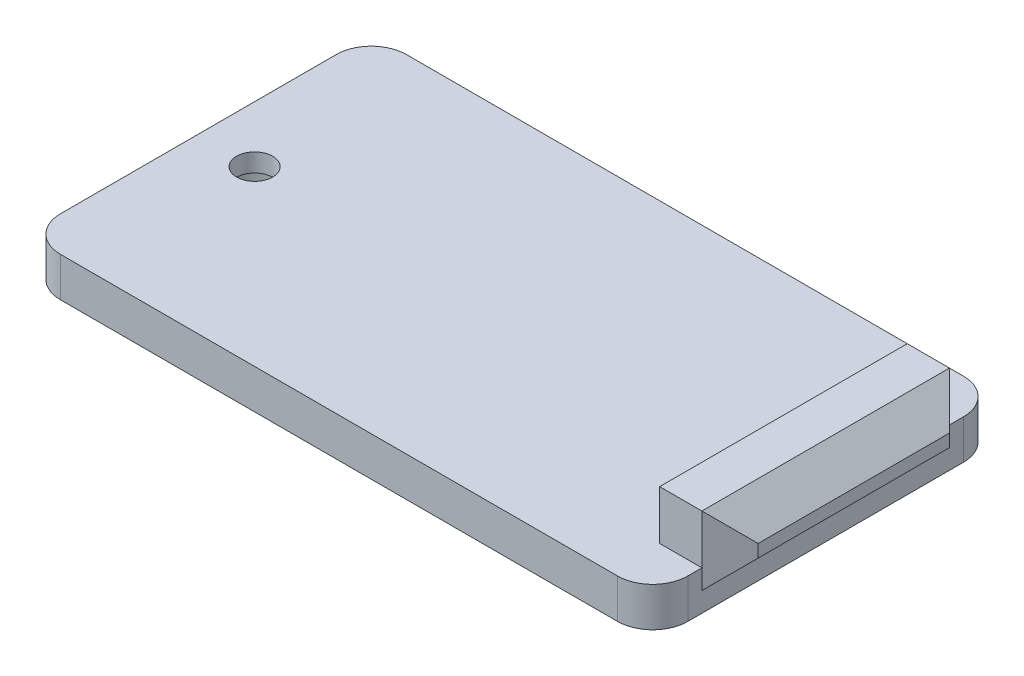
SolidWorks part; units mm, degrees
ref_plane "Front Plane" through (0, 0, 0) normal (0, 0, 1) x (1, 0, 0)
ref_plane "Top Plane" through (0, 0, 0) normal (0, 1, 0) x (1, 0, 0)
ref_plane "Right Plane" through (0, 0, 0) normal (1, 0, 0) x (0, 0, -1)
sketch "Sketch1" plane through (0, 0, 0) normal (0, 1, 0) x (1, 0, 0)
  line L0 (0, 15.621) -> (56.642, 15.621) construction
  line L1 (3.175, 0) -> (53.467, 0)
  line L2 (0, 3.175) -> (0, 28.067)
  line L3 (3.175, 31.242) -> (53.467, 31.242)
  line L4 (56.642, 3.175) -> (56.642, 28.067)
  arc A0 (3.175, 31.242) -> (0, 28.067) centre (3.175, 28.067) ccw
  arc A1 (56.642, 28.067) -> (53.467, 31.242) centre (53.467, 28.067) ccw
  arc A2 (53.467, 0) -> (56.642, 3.175) centre (53.467, 3.175) ccw
  arc A3 (0, 3.175) -> (3.175, 0) centre (3.175, 3.175) ccw
  circle A4 centre (5.08, 15.621) radius 1.632
  dimension "D3" = 6.35
  dimension "D1" = 3.2639
  dimension "D2" = 5.08
  dimension "D4" = 3.175
  dimension "D5" = 3.175
  dimension "D6" = 50.292
  dimension "D7" = 24.892
extrude "Boss-Extrude1" add sketch "Sketch1" along normal blind 3.556
sketch "Sketch2" plane through (0, 0, 0) normal (0, -1, 0) x (1, 0, 0)
  circle A0 centre (5.08, -15.621) radius 3.175
  circle A1 centre (5.08, -15.621) radius 1.6319
  dimension "D1" = 6.35
extrude "Cut-Extrude1" cut sketch "Sketch2" against normal blind 1.905
sketch "Sketch3" plane through (56.642, 0, 0) normal (1, 0, 0) x (0, 0, -1)
  line L0 (3.175, 3.556) -> (3.175, 0) construction
  line L1 (4.445, 1.5875) -> (26.797, 1.5875)
  line L2 (4.445, 1.5875) -> (4.445, 8.1915)
  line L3 (4.445, 8.1915) -> (26.797, 8.1915)
  line L4 (26.797, 1.5875) -> (26.797, 8.1915)
  line L5 (28.067, 3.556) -> (28.067, 0) construction
  line L6 (3.175, 0) -> (28.067, 0) construction
  dimension "D1" = 1.27
  dimension "D2" = 1.27
  dimension "D3" = 1.5875
  dimension "D4" = 6.604
extrude "Boss-Extrude2" add sketch "Sketch3" along normal blind 2.54
chamfer "Chamfer1" distance 2.7305 angle 45 2 edges at (59.182, 1.5875, -15.621) (59.182, 8.1915, -15.621)
sketch "Sketch4" plane through (56.642, 0, 0) normal (-1, 0, 0) x (0, 0, 1)
  line L5 (-26.797, 8.001) -> (-4.445, 8.001)
  line L6 (-26.797, 8.001) -> (-26.797, 3.556)
  line L7 (-26.797, 3.556) -> (-4.445, 3.556)
  line L8 (-4.445, 8.001) -> (-4.445, 3.556)
extrude "Boss-Extrude3" add sketch "Sketch4" along normal blind 3.81
sketch "Sketch5" plane through (0, 0, 0) normal (0, -1, 0) x (1, 0, 0)
  line L0 (12.7, -9.9279) -> (12.7, -31.242) construction
  line L2 (53.467, -31.242) -> (3.175, -31.242) construction
  line L3 (0, -28.067) -> (0, -3.175) construction
  line L4 (0, -15.621) -> (56.642, -15.621) construction
  line L5 (56.642, -26.797) -> (56.642, -4.445) construction
  line L6 (11.1125, -9.271) -> (11.1141, -21.9)
  line L7 (14.2875, -9.271) -> (14.2859, -21.9)
  arc A0 (14.2875, -9.271) -> (11.1125, -9.271) centre (12.7, -9.271) ccw
  arc A1 (11.1141, -21.9) -> (14.2859, -21.9) centre (12.7, -21.971) ccw
  dimension "D2" = 3.175
  dimension "D3" = 3.175
  dimension "D1" = 12.7
  dimension "D4" = 12.7
  dimension "D5" = 6.35
extrude "Cut-Extrude2" cut sketch "Sketch5" against normal blind 1.778
sketch "Sketch6" plane through (0, 0, 0) normal (0, -1, 0) x (1, 0, 0)
  line L0 (14.2871, -12.5095) -> (56.642, -12.5095) construction
  line L1 (14.2859, -21.9) -> (14.2875, -9.271) construction
  line L2 (56.642, -26.797) -> (56.642, -4.445) construction
  line L3 (53.467, -31.242) -> (3.175, -31.242) construction
  text T0 "<b>PGM PIN</b>" font "Arial Rounded MT Bold" height 6.35
  dimension "D1" = 18.7325
extrude "Cut-Extrude3" cut sketch "Sketch6" against normal blind 0.4
chamfer "Chamfer2" distance 2.54 angle 45 2 edges at (59.182, 4.8895, -4.445) (59.182, 4.8895, -26.797)
sketch "Sketch7" plane through (0, 0.4, 0) normal (0, -1, 0) x (1, 0, 0)
  line L0 (22.8836, -17.8227) -> (22.8836, -13.204) construction
  line L1 (21.5342, -13.204) -> (21.5342, -16.637) construction
  line L2 (21.5342, -16.637) -> (19.4705, -13.1805) construction
  line L3 (17.6449, -13.2983) -> (17.6449, -18.0062) construction
  line L4 (18.9942, -18.0013) -> (18.9942, -14.4939) construction
  line L5 (18.9942, -14.4939) -> (21.1101, -17.9827) construction
  line L6 (24.233, -13.2487) -> (24.233, -17.9653) construction
  line L7 (25.6617, -17.9653) -> (25.6617, -13.2487) construction
  line L8 (29.411, -17.5895) -> (30.1067, -17.5895) construction
  line L9 (30.1067, -17.5895) -> (30.1067, -15.9226) construction
  line L10 (30.1067, -15.9226) -> (29.411, -15.9226) construction
  line L11 (29.0811, -18.7007) -> (30.671, -18.7007) construction
  line L12 (31.5355, -17.8748) -> (31.5355, -13.2437) construction
  line L13 (30.1067, -13.2326) -> (30.1067, -14.8114) construction
  line L14 (30.1067, -14.8114) -> (29.1034, -14.8114) construction
  line L15 (37.0322, -13.4992) -> (36.298, -17.272) construction
  line L16 (36.298, -17.272) -> (36.298, -13.1991) construction
  line L17 (34.9486, -13.1978) -> (34.9486, -17.9529) construction
  line L18 (35.8651, -18.7007) -> (36.2422, -18.7007) construction
  line L19 (37.2083, -17.8313) -> (37.9673, -14.5732) construction
  line L20 (37.9673, -14.5732) -> (38.7301, -17.8313) construction
  line L21 (39.7694, -18.7007) -> (40.1452, -18.7007) construction
  line L22 (40.9811, -17.9529) -> (40.9811, -13.1978) construction
  line L23 (39.6317, -13.1991) -> (39.6317, -17.272) construction
  line L24 (39.6317, -17.272) -> (38.9025, -13.5984) construction
  line L25 (43.0895, -15.8432) -> (44.4947, -15.8432) construction
  line L26 (44.3347, -14.732) -> (43.4417, -14.732) construction
  line L27 (43.4417, -14.732) -> (43.4417, -13.9209) construction
  line L28 (42.0924, -13.8924) -> (42.0924, -15.021) construction
  line L29 (51.2267, -18.7007) -> (52.8167, -18.7007) construction
  line L30 (53.6811, -17.8748) -> (53.6811, -13.2437) construction
  line L31 (52.2524, -13.2326) -> (52.2524, -14.8114) construction
  line L32 (52.2524, -14.8114) -> (51.249, -14.8114) construction
  line L33 (22.8836, -17.8227) -> (22.8836, -13.204)
  line L34 (21.5342, -13.204) -> (21.5342, -16.637)
  line L35 (21.5342, -16.637) -> (19.4705, -13.1805)
  line L36 (17.6449, -13.2983) -> (17.6449, -18.0062)
  line L37 (18.9942, -18.0013) -> (18.9942, -14.4939)
  line L38 (18.9942, -14.4939) -> (21.1101, -17.9827)
  line L39 (24.233, -13.2487) -> (24.233, -17.9653)
  line L40 (25.6617, -17.9653) -> (25.6617, -13.2487)
  line L41 (29.411, -17.5895) -> (30.1067, -17.5895)
  line L42 (30.1067, -17.5895) -> (30.1067, -15.9226)
  line L43 (30.1067, -15.9226) -> (29.411, -15.9226)
  line L44 (29.0811, -18.7007) -> (30.671, -18.7007)
  line L45 (31.5355, -17.8748) -> (31.5355, -13.2437)
  line L46 (30.1067, -13.2326) -> (30.1067, -14.8114)
  line L47 (30.1067, -14.8114) -> (29.1034, -14.8114)
  line L48 (37.0322, -13.4992) -> (36.298, -17.272)
  line L49 (36.298, -17.272) -> (36.298, -13.1991)
  line L50 (34.9486, -13.1978) -> (34.9486, -17.9529)
  line L51 (35.8651, -18.7007) -> (36.2422, -18.7007)
  line L52 (37.2083, -17.8313) -> (37.9673, -14.5732)
  line L53 (37.9673, -14.5732) -> (38.7301, -17.8313)
  line L54 (39.7694, -18.7007) -> (40.1452, -18.7007)
  line L55 (40.9811, -17.9529) -> (40.9811, -13.1978)
  line L56 (39.6317, -13.1991) -> (39.6317, -17.272)
  line L57 (39.6317, -17.272) -> (38.9025, -13.5984)
  line L58 (43.0895, -15.8432) -> (44.4947, -15.8432)
  line L59 (44.3347, -14.732) -> (43.4417, -14.732)
  line L60 (43.4417, -14.732) -> (43.4417, -13.9209)
  line L61 (42.0924, -13.8924) -> (42.0924, -15.021)
  line L62 (51.2267, -18.7007) -> (52.8167, -18.7007)
  line L63 (53.6811, -17.8748) -> (53.6811, -13.2437)
  line L64 (52.2524, -13.2326) -> (52.2524, -14.8114)
  line L65 (52.2524, -14.8114) -> (51.249, -14.8114)
  line L69 (51.5566, -17.5895) -> (52.2524, -17.5895)
  line L70 (52.2524, -17.5895) -> (52.2524, -15.9226)
  line L71 (52.2524, -15.9226) -> (51.5566, -15.9226)
  line L72 (51.5566, -17.5895) -> (52.2524, -17.5895)
  line L73 (52.2524, -17.5895) -> (52.2524, -15.9226)
  line L74 (52.2524, -15.9226) -> (51.5566, -15.9226)
  spline S0 degree 3 poles (1694.5755, 1077.0446) (-0.9521, -10.018) (16.4237, -10.1614) (21.3024, -18.2955) (21.3908, -18.4248) (21.4855, -18.5395) (21.6023, -18.636) (21.7165, -18.702) (21.8212, -18.7424) (21.909, -18.7651) (25.6619, -19.2283) (30.4113, -0.5881) (-74.1786, -2016.3877) knots -20.662899 -20.662899 -20.662899 -20.662899 0.149245 0.276601 0.389391 0.49681 0.605632 0.72403 0.787951 0.85429 0.924647 9.163349 9.163349 9.163349 9.163349 only from (21.1101, -17.9827) to (22.1035, -18.7801) construction
  spline S1 degree 3 poles (219.4888, -2008.9999) (13.2158, 3.8808) (19.0049, -19.4639) (22.3265, -18.7508) (22.432, -18.7088) (22.5312, -18.6519) (22.6234, -18.5835) (22.7009, -18.502) (24.5279, -16.1058) (3.0005, -0.21) (1757.2202, -1014.0759) knots -10.891564 -10.891564 -10.891564 -10.891564 0.125807 0.249903 0.374306 0.502706 0.630625 0.755401 0.87671 10.617247 10.617247 10.617247 10.617247 only from (22.1035, -18.7801) to (22.8142, -18.3126) construction
  spline S2 degree 3 poles (1955.4913, -532.5395) (-0.8488, -18.4154) (22.3614, -21.2427) (22.868, -18.0952) (23.3749, -13.5564) (0.9699, -7.6141) (2019.659, -130.1936) knots -18.460388 -18.460388 -18.460388 -18.460388 0.206623 0.439918 0.70566 27.741178 27.741178 27.741178 27.741178 only from (22.8142, -18.3126) to (22.8836, -17.8227) construction
  spline S3 degree 3 poles (2015.117, 161.9076) (-4.3478, -24.2033) (23.7389, -17.199) (22.8457, -12.8793) (22.7913, -12.7442) (22.7151, -12.631) (22.6207, -12.5408) (22.5099, -12.4763) (19.3608, -11.4724) (11.7065, -41.2288) (305.4229, 1967.3468) knots -11.230317 -11.230317 -11.230317 -11.230317 0.155135 0.293175 0.420208 0.539589 0.652988 0.763719 0.877627 9.330939 9.330939 9.330939 9.330939 only from (22.8836, -13.204) to (22.2486, -12.4301) construction
  spline S4 degree 3 poles (-221.9847, 1972.5129) (33.2019, -41.098) (25.6271, -11.4529) (21.9492, -12.4775) (21.8233, -12.5449) (21.7187, -12.639) (21.6359, -12.7554) (21.576, -12.8898) (20.6395, -16.9841) (48.7131, -24.0672) (-1968.7834, 183.0792) knots -9.165477 -9.165477 -9.165477 -9.165477 0.133965 0.257434 0.373611 0.491036 0.609102 0.73139 0.859882 11.130855 11.130855 11.130855 11.130855 only from (22.2486, -12.4301) to (21.5342, -13.204) construction
  spline S5 degree 3 poles (1656.6632, 1135.4192) (16.0773, -34.8465) (23.9453, -19.395) (19.2712, -12.8948) (19.168, -12.7596) (19.0501, -12.6437) (18.9231, -12.5453) (18.7807, -12.4775) (14.9393, -11.4463) (7.1492, -42.1909) (257.016, 1973.2581) knots -17.714942 -17.714942 -17.714942 -17.714942 0.132477 0.263732 0.391458 0.516373 0.636572 0.752789 0.870676 9.55723 9.55723 9.55723 9.55723 only from (19.4705, -13.1805) to (18.4572, -12.4301) construction
  spline S6 degree 3 poles (-199.2692, 1975.6658) (30.3091, -42.3393) (22.3802, -11.4241) (18.1045, -12.478) (17.9603, -12.5449) (17.8435, -12.6436) (17.7512, -12.769) (17.6894, -12.923) (16.68, -17.5496) (47.2481, -25.402) (-1972.9092, 179.8342) knots -9.252194 -9.252194 -9.252194 -9.252194 0.140574 0.265343 0.378552 0.487786 0.598508 0.718065 0.850401 10.972845 10.972845 10.972845 10.972845 only from (18.4572, -12.4301) to (17.6449, -13.2983) construction
  spline S7 degree 3 poles (-1971.9914, -221.0692) (45.7061, -7.1326) (16.7501, -14.3175) (17.6857, -18.322) (17.7427, -18.457) (17.8227, -18.5739) (17.9276, -18.6675) (18.0551, -18.7345) (21.9641, -19.7378) (29.2769, 9.5928) (-196.239, -2007.1892) knots -9.821137 -9.821137 -9.821137 -9.821137 0.139787 0.268103 0.388435 0.504223 0.619109 0.736039 0.86109 10.613704 10.613704 10.613704 10.613704 only from (17.6449, -18.0062) to (18.3654, -18.7801) construction
  spline S8 degree 3 poles (285.63, -2000.738) (8.0695, 9.4364) (15.4308, -19.7154) (18.6248, -18.7353) (18.7345, -18.6708) (18.8287, -18.5817) (18.9032, -18.4678) (18.9582, -18.332) (19.8193, -13.7643) (-7.3619, -7.0829) (2014.0061, -158.3941) knots -8.414127 -8.414127 -8.414127 -8.414127 0.121086 0.23344 0.343994 0.455662 0.57424 0.702085 0.841831 12.827612 12.827612 12.827612 12.827612 only from (18.3654, -18.7801) to (18.9942, -18.0013) construction
  spline S9 degree 3 poles (2015.8485, 184.4309) (-3.4376, -24.7913) (26.5834, -17.2335) (25.6202, -12.9015) (25.5631, -12.7572) (25.4784, -12.6394) (25.3767, -12.5468) (25.262, -12.4769) (21.9114, -11.4795) (14.7129, -40.1038) (275.6513, 1971.7398) knots -10.696765 -10.696765 -10.696765 -10.696765 0.157586 0.29838 0.425876 0.546132 0.660428 0.770664 0.881724 9.364177 9.364177 9.364177 9.364177 only from (25.6617, -13.2487) to (24.9932, -12.4301) construction
  spline S10 degree 3 poles (-202.4906, 1974.5266) (36.1726, -41.848) (28.5549, -11.4334) (24.6724, -12.4784) (24.5387, -12.5492) (24.4273, -12.6474) (24.3387, -12.7689) (24.2771, -12.9117) (23.2907, -17.1097) (52.9605, -24.6484) (-1964.8958, 194.4319) knots -9.066225 -9.066225 -9.066225 -9.066225 0.135671 0.258584 0.375206 0.491184 0.60762 0.728719 0.85756 10.764543 10.764543 10.764543 10.764543 only from (24.9932, -12.4301) to (24.233, -13.2487) construction
  spline S11 degree 3 poles (-1966.1581, -213.3588) (52.5085, -6.7201) (23.3014, -14.0619) (24.2766, -18.3016) (24.3392, -18.444) (24.4269, -18.5653) (24.5389, -18.6624) (24.6727, -18.7316) (28.5344, -19.7815) (36.2765, 10.7612) (-210.5409, -2004.8083) knots -9.871041 -9.871041 -9.871041 -9.871041 0.141749 0.271807 0.392253 0.508926 0.624493 0.740892 0.864054 10.044378 10.044378 10.044378 10.044378 only from (24.233, -17.9653) to (24.9932, -18.7801) construction
  spline S12 degree 3 poles (296.3055, -2000.247) (14.3991, 9.2996) (21.9419, -19.7415) (25.2631, -18.7328) (25.3788, -18.6656) (25.4801, -18.5731) (25.5625, -18.4554) (25.6206, -18.3122) (26.5783, -13.9553) (-3.3031, -6.554) (2016.8183, -204.938) knots -8.324459 -8.324459 -8.324459 -8.324459 0.119507 0.230748 0.341537 0.454545 0.574394 0.701135 0.842157 11.766884 11.766884 11.766884 11.766884 only from (24.9932, -18.7801) to (25.6617, -17.9653) construction
  spline S13 degree 3 poles (-1141.57, -1639.3969) (37.7723, 4.8762) (26.0647, -16.1496) (28.5071, -17.457) (28.6151, -17.497) (28.7398, -17.5323) (28.8829, -17.5566) (29.0429, -17.5771) (36.1961, -17.9955) (43.6576, 0.9749) (13.0193, -2017.4401) knots -7.112256 -7.112256 -7.112256 -7.112256 0.082202 0.173662 0.275948 0.391262 0.521073 0.665415 0.824521 19.752253 19.752253 19.752253 19.752253 only from (28.3431, -17.3464) to (29.411, -17.5895) construction
  spline S14 degree 3 poles (-35.0501, 1982.9336) (42.7836, -38.1259) (35.4441, -15.3837) (29.0175, -15.9412) (28.8465, -15.9663) (28.6943, -16.003) (28.5598, -16.0511) (28.443, -16.1114) (28.3445, -16.1861) (28.2618, -16.2721) (28.1991, -16.3738) (28.154, -16.4893) (27.3637, -20.2232) (54.0403, -26.533) (-1963.7752, 161.9613) knots -10.706041 -10.706041 -10.706041 -10.706041 0.119625 0.228284 0.326363 0.415267 0.495857 0.570243 0.639451 0.706531 0.77329 0.842541 0.917764 7.268042 7.268042 7.268042 7.268042 only from (29.411, -15.9226) to (28.1224, -16.7598) construction
  spline S15 degree 3 poles (-1952.1927, -296.1847) (58.1274, -4.8115) (27.0921, -13.2814) (28.1735, -17.0867) (29.6461, -20.2637) (58.4433, -4.7638) (-1619.0052, -1151.4131) knots -17.588032 -17.588032 -17.588032 -17.588032 0.269063 0.519036 0.759812 16.445294 16.445294 16.445294 16.445294 only from (28.1224, -16.7598) to (28.3431, -17.3464) construction
  spline S16 degree 3 poles (-41.9846, 1983.8314) (45.3761, -40.1417) (36.3747, -14.0962) (28.5459, -14.8405) (28.2911, -14.8788) (28.0556, -14.9359) (27.8379, -15.0079) (27.6383, -15.0949) (27.4587, -15.2018) (27.2963, -15.3216) (27.1541, -15.4581) (27.0304, -15.6078) (26.9251, -15.7712) (26.8414, -15.949) (26.7731, -16.1388) (26.7269, -16.3429) (25.9325, -22.6554) (51.2956, -30.5501) (-1970.3258, 90.9039) knots -6.410635 -6.410635 -6.410635 -6.410635 0.081805 0.159007 0.231173 0.299492 0.363591 0.424766 0.483204 0.53989 0.595011 0.649378 0.703763 0.758786 0.81516 0.873993 0.935286 6.184234 6.184234 6.184234 6.184234 only from (29.1034, -14.8114) to (26.6936, -16.7858) construction
  spline S17 degree 3 poles (-1969.3893, -140.0701) (51.6371, -3.9375) (25.9499, -11.4626) (26.7257, -17.1977) (26.7665, -17.393) (26.8278, -17.5782) (26.9059, -17.7532) (27.0027, -17.9162) (27.1185, -18.066) (27.2493, -18.2044) (27.3998, -18.3268) (27.5676, -18.4322) (32.6459, -20.8359) (47.4639, 2.6822) (-664.7553, -1894.6989) knots -7.048453 -7.048453 -7.048453 -7.048453 0.088961 0.174891 0.258882 0.340892 0.421162 0.500878 0.579938 0.660187 0.741194 0.824606 0.910207 7.826152 7.826152 7.826152 7.826152 only from (26.6936, -16.7858) to (27.9524, -18.5854) construction
  spline S18 degree 3 poles (-461.0485, -1957.8289) (24.0357, 0.2052) (23.9754, -17.7978) (28.1727, -18.6377) (28.2977, -18.6574) (28.4334, -18.6734) (28.5798, -18.6857) (28.7375, -18.6937) (35.7709, -18.9905) (43.1078, -1.3668) (9.9605, -2018.5164) knots -10.968522 -10.968522 -10.968522 -10.968522 0.093582 0.195965 0.307413 0.42705 0.556114 0.694736 0.843057 19.111476 19.111476 19.111476 19.111476 only from (27.9524, -18.5854) to (29.0811, -18.7007) construction
  spline S19 degree 3 poles (123.9355, -2016.4485) (22.4379, 0.8817) (27.1719, -19.093) (30.8748, -18.6893) (30.9674, -18.6751) (31.0529, -18.6541) (31.1316, -18.6271) (31.2024, -18.5933) (31.2671, -18.5548) (31.3241, -18.5087) (31.375, -18.4556) (31.418, -18.3948) (31.4546, -18.3265) (31.4839, -18.2506) (31.5078, -18.1672) (31.5232, -18.0761) (31.9325, -14.114) (13.6058, -9.1312) (2028.9036, -118.2922) knots -7.859646 -7.859646 -7.859646 -7.859646 0.077201 0.149354 0.216632 0.280407 0.340294 0.396897 0.450458 0.503438 0.555489 0.60953 0.664538 0.723366 0.785866 0.85241 0.92367 9.425162 9.425162 9.425162 9.425162 only from (30.671, -18.7007) to (31.5355, -17.8748) construction
  spline S20 degree 3 poles (2024.5224, 153.4495) (3.4334, -24.4212) (32.4228, -17.3367) (31.4958, -12.8999) (31.4372, -12.7578) (31.3561, -12.6387) (31.2536, -12.5461) (31.1365, -12.4766) (27.6638, -11.4763) (20.4785, -40.3907) (269.8756, 1973.1764) knots -10.879349 -10.879349 -10.879349 -10.879349 0.15481 0.29374 0.419708 0.538233 0.652017 0.763548 0.877091 9.613357 9.613357 9.613357 9.613357 only from (31.5355, -13.2437) to (30.8583, -12.4301) construction
  spline S21 degree 3 poles (-192.9819, 1974.8971) (41.7689, -41.3433) (34.3515, -11.4431) (30.5459, -12.4783) (30.4149, -12.55) (30.3036, -12.6463) (30.2142, -12.7655) (30.1524, -12.9056) (29.1429, -16.8859) (59.2654, -24.6048) (-1956.5875, 216.7235) knots -9.063499 -9.063499 -9.063499 -9.063499 0.133395 0.256831 0.374018 0.491652 0.610199 0.730976 0.859706 10.470605 10.470605 10.470605 10.470605 only from (30.8583, -12.4301) to (30.1067, -13.2326) construction
  spline S22 degree 3 poles (2025.2351, 218.3807) (36.3034, -39.4717) (41.2772, -25.9219) (38.8533, -13.3404) (38.8269, -13.2298) (38.7947, -13.1009) (38.747, -12.9534) (38.6808, -12.8168) (38.6149, -12.7167) (38.5564, -12.6477) (38.487, -12.5867) (38.409, -12.5323) (38.3221, -12.485) (38.2241, -12.4538) (34.9329, -11.8089) (29.2405, -35.9793) (223.6773, 1978.7209) knots -23.288307 -23.288307 -23.288307 -23.288307 0.085751 0.163161 0.233313 0.294435 0.407254 0.517243 0.57198 0.626896 0.68281 0.74114 0.801241 0.863651 0.929305 6.936938 6.936938 6.936938 6.936938 only from (38.9025, -13.5984) to (38.0045, -12.4301) construction
  spline S23 degree 3 poles (-121.2426, 1981.1451) (48.7647, -39.2041) (42.0185, -11.5876) (37.6839, -12.4673) (37.5515, -12.5239) (37.4423, -12.6017) (37.354, -12.6908) (37.2797, -12.7814) (37.2216, -12.8745) (37.1809, -12.9737) (37.1497, -13.0824) (37.1134, -13.2047) (34.4734, -22.5334) (43.2594, -34.9159) (-1900.4937, 482.1352) knots -7.932757 -7.932757 -7.932757 -7.932757 0.107759 0.20426 0.291925 0.375204 0.453432 0.526045 0.594111 0.657905 0.725931 0.805738 0.896595 18.867428 18.867428 18.867428 18.867428 only from (38.0045, -12.4301) to (37.0322, -13.4992) construction
  spline S24 degree 3 poles (2030.5792, 136.7004) (9.4802, -24.0699) (37.1401, -17.3276) (36.261, -12.8702) (36.2046, -12.7356) (36.127, -12.6243) (36.0312, -12.5379) (35.9224, -12.4735) (32.7034, -11.5264) (25.7733, -39.4667) (283.8166, 1972.0348) knots -11.659036 -11.659036 -11.659036 -11.659036 0.158568 0.299864 0.427305 0.546437 0.660037 0.770128 0.882171 9.537425 9.537425 9.537425 9.537425 only from (36.298, -13.1991) to (35.6692, -12.4301) construction
  spline S25 degree 3 poles (-188.2538, 1974.9316) (46.6426, -40.899) (39.2228, -11.4693) (35.3611, -12.476) (35.2337, -12.5427) (35.1293, -12.6365) (35.0481, -12.7515) (34.9889, -12.8845) (34.0623, -16.8967) (62.7798, -23.8843) (-1955.8719, 177.9822) knots -9.562481 -9.562481 -9.562481 -9.562481 0.138683 0.263459 0.38107 0.496625 0.612837 0.732384 0.860436 10.888562 10.888562 10.888562 10.888562 only from (35.6692, -12.4301) to (34.9486, -13.1978) construction
  spline S26 degree 3 poles (-1959.7061, -163.8499) (55.5588, -9.9892) (34.4868, -14.891) (34.9635, -18.1416) (34.9808, -18.2266) (35.01, -18.3027) (35.0448, -18.3728) (35.0881, -18.4348) (35.1398, -18.4889) (35.2193, -18.5508) (35.3361, -18.6122) (35.4947, -18.6635) (40.3073, -19.5518) (47.5603, 9.0529) (-118.7206, -2012.6573) knots -7.056809 -7.056809 -7.056809 -7.056809 0.073258 0.141589 0.204417 0.26493 0.321406 0.377256 0.431625 0.486361 0.59978 0.721317 0.854318 11.386728 11.386728 11.386728 11.386728 only from (34.9486, -17.9529) to (35.8651, -18.7007) construction
  spline S27 degree 3 poles (78.9418, -2018.1494) (24.049, 0.0457) (30.5727, -19.1483) (36.5456, -18.6865) (36.6679, -18.6647) (36.7706, -18.6339) (36.8568, -18.5916) (36.9275, -18.5338) (36.987, -18.4649) (37.0341, -18.3794) (37.0737, -18.2752) (37.1197, -18.1503) (41.1539, -3.7558) (36.9318, 11.2678) (2033.4968, -136.8195) knots -11.807636 -11.807636 -11.807636 -11.807636 0.112068 0.209398 0.292691 0.362757 0.425565 0.48562 0.546098 0.608621 0.681737 0.771371 0.877705 30.890178 30.890178 30.890178 30.890178 only from (36.2422, -18.7007) to (37.2083, -17.8313) construction
  spline S28 degree 3 poles (-1901.4193, -503.2352) (48.8677, 1.0529) (36.532, -10.4403) (38.8161, -18.1361) (38.8585, -18.2577) (38.898, -18.3606) (38.9482, -18.4455) (39.0116, -18.517) (39.0915, -18.5754) (39.1869, -18.6233) (39.3015, -18.6593) (39.4375, -18.6821) (44.7925, -19.2536) (51.4103, 4.294) (-52.9455, -2016.4676) knots -15.308363 -15.308363 -15.308363 -15.308363 0.112517 0.209912 0.293293 0.362854 0.423786 0.484131 0.547311 0.614894 0.690901 0.77998 0.882598 11.151583 11.151583 11.151583 11.151583 only from (38.7301, -17.8313) to (39.7694, -18.7007) construction
  spline S29 degree 3 poles (192.2145, -2012.8569) (29.0024, 7.1901) (35.8575, -19.4882) (40.4788, -18.6668) (40.6228, -18.6191) (40.7296, -18.5615) (40.8042, -18.5038) (40.8514, -18.4503) (40.8935, -18.3894) (40.9243, -18.3176) (40.9515, -18.2392) (40.9676, -18.151) (41.4103, -14.5144) (21.6469, -9.5248) (2036.9815, -143.823) knots -10.455968 -10.455968 -10.455968 -10.455968 0.137215 0.26181 0.378149 0.487488 0.541352 0.595616 0.652214 0.712235 0.775857 0.844249 0.919473 9.258261 9.258261 9.258261 9.258261 only from (40.1452, -18.7007) to (40.9811, -17.9529) construction
  spline S30 degree 3 poles (2034.3983, 148.7091) (13.8838, -24.2286) (41.83, -17.3067) (40.9438, -12.8674) (40.8884, -12.7323) (40.81, -12.6218) (40.7142, -12.5365) (40.6049, -12.4734) (37.3529, -11.522) (30.3235, -39.6964) (290.7469, 1971.7676) knots -11.583025 -11.583025 -11.583025 -11.583025 0.159165 0.300011 0.428063 0.545915 0.658415 0.767606 0.880349 9.598993 9.598993 9.598993 9.598993 only from (40.9811, -13.1978) to (40.3486, -12.4301) construction
  spline S31 degree 3 poles (-175.4537, 1975.7855) (51.1498, -40.4839) (43.9049, -11.4778) (40.0432, -12.4757) (39.9166, -12.5431) (39.8125, -12.6365) (39.7309, -12.7517) (39.6723, -12.8854) (38.742, -16.8812) (67.5573, -23.9622) (-1950.4516, 184.616) knots -9.575233 -9.575233 -9.575233 -9.575233 0.136891 0.261922 0.378854 0.494646 0.611095 0.731837 0.860151 10.873259 10.873259 10.873259 10.873259 only from (40.3486, -12.4301) to (39.6317, -13.1991) construction
  spline S32 degree 3 poles (-1951.0469, -180.2941) (68.1508, -4.8637) (41.369, -11.2886) (42.121, -15.3092) (42.1595, -15.4312) (42.2158, -15.5361) (42.2877, -15.6231) (42.3724, -15.6932) (42.4683, -15.7495) (42.5775, -15.7866) (42.6956, -15.8113) (42.8207, -15.8299) (47.8379, -16.2612) (53.6135, 2.9126) (-23.8507, -2014.6918) knots -7.876478 -7.876478 -7.876478 -7.876478 0.103568 0.196096 0.280628 0.358765 0.432833 0.5051 0.577777 0.654212 0.734732 0.819236 0.907276 10.806206 10.806206 10.806206 10.806206 only from (42.0924, -15.021) to (43.0895, -15.8432) construction
  spline S33 degree 3 poles (275.4815, -2002.3731) (34.5243, 10.7675) (41.3344, -16.6573) (44.7512, -15.8077) (44.8614, -15.7594) (44.9539, -15.6889) (45.0313, -15.6049) (45.0845, -15.5061) (45.9895, -12.6451) (18.1526, -5.2749) (2021.7964, -319.2772) knots -10.676899 -10.676899 -10.676899 -10.676899 0.144369 0.276441 0.400049 0.52257 0.642148 0.758736 0.875089 10.055862 10.055862 10.055862 10.055862 only from (44.4947, -15.8432) to (45.1247, -15.2814) construction
  spline S34 degree 3 poles (2026.8724, 253.8756) (15.4003, -25.6663) (46.0992, -18.1349) (45.0793, -15.0231) (45.0121, -14.9233) (44.9174, -14.8487) (44.7999, -14.7967) (44.6633, -14.7588) (39.8655, -14.0417) (33.3806, -39.8097) (161.0018, 1981.8187) knots -8.465606 -8.465606 -8.465606 -8.465606 0.128037 0.242249 0.346183 0.452121 0.566739 0.694642 0.83846 13.768596 13.768596 13.768596 13.768596 only from (45.1247, -15.2814) to (44.3347, -14.732) construction
  spline S35 degree 3 poles (-801.923, 1798.5112) (40.2185, -37.6529) (37.6775, -16.2692) (43.7923, -13.7644) (43.9732, -13.7) (44.1579, -13.6436) (44.3477, -13.5968) (44.5447, -13.5653) (50.7698, -12.9275) (58.1801, -36.455) (-40.3559, 1984.5415) knots -12.207121 -12.207121 -12.207121 -12.207121 0.121821 0.243575 0.365559 0.487311 0.611204 0.737234 0.866927 12.512728 12.512728 12.512728 12.512728 only from (43.4417, -13.9209) to (44.9561, -13.5414) construction
  spline S36 degree 3 poles (162.2707, 1982.9416) (32.6747, -37.6241) (39.8288, -12.8267) (45.3359, -13.5716) (45.5118, -13.6122) (45.6772, -13.6693) (45.8317, -13.7444) (45.9763, -13.8352) (46.1102, -13.9426) (46.2314, -14.0673) (46.342, -14.207) (46.437, -14.3639) (46.5184, -14.5367) (46.5833, -14.7257) (46.6345, -14.9307) (46.6691, -15.1515) (47.3704, -22.2923) (22.582, -30.636) (2044.9799, 63.7074) knots -5.196502 -5.196502 -5.196502 -5.196502 0.063411 0.124084 0.182145 0.23819 0.293421 0.348374 0.403414 0.459551 0.51666 0.575865 0.637025 0.701566 0.769344 0.841653 0.918173 7.721568 7.721568 7.721568 7.721568 only from (44.9561, -13.5414) to (46.6961, -15.6361) construction
  spline S37 degree 3 poles (2044.9407, -97.0342) (22.4669, -1.4911) (47.3791, -9.4048) (46.6683, -16.0971) (46.6291, -16.3112) (46.5736, -16.5116) (46.5038, -16.6974) (46.4226, -16.8677) (46.328, -17.0221) (46.2194, -17.1583) (46.1018, -17.2798) (45.9724, -17.3833) (45.8343, -17.4722) (45.6856, -17.5443) (45.5267, -17.6007) (45.3573, -17.6393) (40.2488, -18.3872) (33.265, 7.7445) (173.5845, -2013.4235) knots -6.489454 -6.489454 -6.489454 -6.489454 0.079365 0.154968 0.22725 0.296715 0.36248 0.425308 0.485045 0.542988 0.599083 0.653735 0.708175 0.762869 0.818537 0.87626 0.936326 5.967107 5.967107 5.967107 5.967107 only from (46.6961, -15.6361) to (44.9895, -17.6689) construction
  spline S38 degree 3 poles (-46.4653, -2015.5416) (57.1883, 5.3714) (50.2767, -18.3069) (44.6271, -17.6441) (44.4698, -17.6087) (44.3302, -17.5586) (44.2075, -17.4969) (44.0971, -17.4305) (44.0011, -17.3553) (43.9141, -17.2714) (43.8323, -17.1705) (43.7398, -17.0547) (38.5946, -9.8533) (46.3312, 5.8605) (-1635.6714, -1102.892) knots -9.081995 -9.081995 -9.081995 -9.081995 0.105862 0.202788 0.291028 0.371551 0.446938 0.517402 0.584022 0.64773 0.716501 0.798147 0.892479 15.320467 15.320467 15.320467 15.320467 only from (44.9895, -17.6689) to (43.5348, -16.7598) construction
  spline S39 degree 3 poles (1337.2945, 1508.2977) (27.7541, -45.4864) (46.2523, -18.3006) (43.3015, -16.5711) (40.103, -15.4035) (30.9099, -46.0576) (406.804, 1950.0702) knots -16.247565 -16.247565 -16.247565 -16.247565 0.254155 0.505003 0.75336 17.192274 17.192274 17.192274 17.192274 only from (43.5348, -16.7598) to (43.0126, -16.5105) construction
  spline S40 degree 3 poles (-174.1779, 1971.6212) (53.5388, -43.809) (46.4777, -15.6036) (42.7184, -16.5535) (42.5908, -16.6168) (42.4815, -16.7026) (42.3915, -16.8014) (42.3257, -16.9086) (41.3083, -19.5551) (70.3718, -27.8056) (-1924.7974, 343.9056) knots -10.365944 -10.365944 -10.365944 -10.365944 0.144122 0.279276 0.409838 0.540303 0.666629 0.782068 0.891637 8.505634 8.505634 8.505634 8.505634 only from (43.0126, -16.5105) to (42.2759, -17.1381) construction
  spline S41 degree 3 poles (-1939.155, -288.0931) (65.7479, -7.6604) (41.503, -14.2651) (42.3139, -17.3723) (42.3623, -17.5008) (42.431, -17.6366) (42.518, -17.7756) (42.6263, -17.9134) (42.7544, -18.0475) (42.9009, -18.1807) (43.0718, -18.3044) (43.2663, -18.4189) (43.4856, -18.521) (43.7268, -18.6127) (43.9889, -18.6888) (44.2706, -18.7409) (52.3496, -19.634) (61.9193, 7.7545) (-43.6778, -2016.7306) knots -2.748306 -2.748306 -2.748306 -2.748306 0.03306 0.069223 0.110316 0.155816 0.20519 0.256848 0.312331 0.371015 0.433767 0.500772 0.572764 0.649928 0.731544 0.816657 0.905969 7.996497 7.996497 7.996497 7.996497 only from (42.2759, -17.1381) to (44.8792, -18.7801) construction
  spline S42 degree 3 poles (128.6878, -2016.8671) (26.3882, 9.9101) (36.7763, -19.7673) (45.5961, -18.7314) (45.9279, -18.6618) (46.2409, -18.5672) (46.5321, -18.4435) (46.8021, -18.2966) (47.0488, -18.1235) (47.2729, -17.9275) (47.4723, -17.707) (47.6454, -17.463) (47.794, -17.1981) (47.9131, -16.9111) (48.0096, -16.6072) (48.0748, -16.2861) (49.1264, -8.0478) (19.1729, 2.1125) (2045.1748, -122.5233) knots -4.966157 -4.966157 -4.966157 -4.966157 0.072177 0.140669 0.206479 0.269813 0.331105 0.390807 0.44883 0.506607 0.564164 0.621932 0.680789 0.741005 0.802957 0.866543 0.931921 5.641671 5.641671 5.641671 5.641671 only from (44.8792, -18.7801) to (48.1249, -15.6051) construction
  spline S43 degree 3 poles (2045.4494, 85.6338) (18.926, -33.3522) (49.1358, -23.2077) (48.0744, -14.9156) (48.0056, -14.5931) (47.9074, -14.2887) (47.7835, -14.0034) (47.636, -13.7379) (47.4606, -13.4965) (47.2633, -13.2755) (47.0415, -13.0798) (46.7996, -12.9066) (46.5347, -12.7616) (46.2497, -12.6417) (45.947, -12.5454) (45.6264, -12.4799) (37.3297, -11.4299) (27.1511, -41.384) (149.1014, 1984.77) knots -4.727167 -4.727167 -4.727167 -4.727167 0.069885 0.13706 0.201523 0.264379 0.325617 0.384979 0.443395 0.501491 0.559607 0.617738 0.676863 0.737588 0.800063 0.864185 0.930603 5.73159 5.73159 5.73159 5.73159 only from (48.1249, -15.6051) to (44.9424, -12.4301) construction
  spline S44 degree 3 poles (-26.6544, 1986.2283) (62.1856, -37.8449) (52.6632, -11.6712) (44.3365, -12.463) (44.0491, -12.5065) (43.7726, -12.5711) (43.5015, -12.6522) (43.2327, -12.7541) (35.6128, -16.0228) (39.6467, -43.2113) (-848.2835, 1777.4612) knots -10.298585 -10.298585 -10.298585 -10.298585 0.132165 0.260051 0.383597 0.503454 0.622655 0.745058 0.870724 11.213186 11.213186 11.213186 11.213186 only from (44.9424, -12.4301) to (42.6951, -13.0106) construction
  spline S45 degree 3 poles (-953.2738, 1721.3159) (59.9637, -24.0779) (46.5462, -10.5513) (42.4888, -13.1321) (42.4017, -13.1935) (42.3265, -13.2559) (42.2626, -13.3189) (42.2101, -13.3848) (42.1695, -13.4539) (42.1387, -13.5269) (42.1177, -13.6059) (42.1036, -13.6931) (41.7005, -17.3376) (61.7508, -22.0118) (-1955.6485, 78.8439) knots -12.280943 -12.280943 -12.280943 -12.280943 0.110523 0.211747 0.304882 0.389442 0.46753 0.539224 0.609598 0.676558 0.746162 0.823055 0.907947 10.33633 10.33633 10.33633 10.33633 only from (42.6951, -13.0106) to (42.0924, -13.8924) construction
  spline S46 degree 3 poles (-19.839, 1983.8314) (67.5217, -40.1417) (58.5203, -14.0962) (50.6916, -14.8405) (50.4367, -14.8788) (50.2012, -14.9359) (49.9835, -15.0079) (49.7839, -15.0949) (49.6043, -15.2018) (49.4419, -15.3216) (49.2997, -15.4581) (49.176, -15.6078) (49.0707, -15.7712) (48.987, -15.949) (48.9187, -16.1388) (48.8725, -16.3429) (48.0782, -22.6554) (73.4412, -30.5501) (-1948.1802, 90.9039) knots -6.410635 -6.410635 -6.410635 -6.410635 0.081805 0.159007 0.231173 0.299492 0.363591 0.424766 0.483204 0.53989 0.595011 0.649378 0.703763 0.758786 0.81516 0.873993 0.935286 6.184234 6.184234 6.184234 6.184234 only from (51.249, -14.8114) to (48.8392, -16.7858) construction
  spline S47 degree 3 poles (-1947.2437, -140.0701) (73.7827, -3.9375) (48.0955, -11.4626) (48.8713, -17.1977) (48.9121, -17.393) (48.9734, -17.5782) (49.0516, -17.7532) (49.1483, -17.9162) (49.2641, -18.066) (49.3949, -18.2044) (49.5454, -18.3268) (49.7132, -18.4322) (54.7915, -20.8359) (69.6095, 2.6822) (-642.6097, -1894.6989) knots -7.048453 -7.048453 -7.048453 -7.048453 0.088961 0.174891 0.258882 0.340892 0.421162 0.500878 0.579938 0.660187 0.741194 0.824606 0.910207 7.826152 7.826152 7.826152 7.826152 only from (48.8392, -16.7858) to (50.0981, -18.5854) construction
  spline S48 degree 3 poles (-438.9029, -1957.8289) (46.1814, 0.2052) (46.121, -17.7978) (50.3184, -18.6377) (50.4433, -18.6574) (50.579, -18.6734) (50.7255, -18.6857) (50.8831, -18.6937) (57.9165, -18.9905) (65.2534, -1.3668) (32.1061, -2018.5164) knots -10.968522 -10.968522 -10.968522 -10.968522 0.093582 0.195965 0.307413 0.42705 0.556114 0.694736 0.843057 19.111476 19.111476 19.111476 19.111476 only from (50.0981, -18.5854) to (51.2267, -18.7007) construction
  spline S49 degree 3 poles (146.0811, -2016.4485) (44.5835, 0.8817) (49.3176, -19.093) (53.0204, -18.6893) (53.113, -18.6751) (53.1985, -18.6541) (53.2772, -18.6271) (53.348, -18.5933) (53.4127, -18.5548) (53.4698, -18.5087) (53.5206, -18.4556) (53.5636, -18.3948) (53.6002, -18.3265) (53.6295, -18.2506) (53.6534, -18.1672) (53.6688, -18.0761) (54.0781, -14.114) (35.7514, -9.1312) (2051.0492, -118.2922) knots -7.859646 -7.859646 -7.859646 -7.859646 0.077201 0.149354 0.216632 0.280407 0.340294 0.396897 0.450458 0.503438 0.555489 0.60953 0.664538 0.723366 0.785866 0.85241 0.92367 9.425162 9.425162 9.425162 9.425162 only from (52.8167, -18.7007) to (53.6811, -17.8748) construction
  spline S50 degree 3 poles (2046.668, 153.4495) (25.579, -24.4212) (54.5684, -17.3367) (53.6414, -12.8999) (53.5828, -12.7578) (53.5017, -12.6387) (53.3993, -12.5461) (53.2821, -12.4766) (49.8094, -11.4763) (42.6241, -40.3907) (292.0212, 1973.1764) knots -10.879349 -10.879349 -10.879349 -10.879349 0.15481 0.29374 0.419708 0.538233 0.652017 0.763548 0.877091 9.613357 9.613357 9.613357 9.613357 only from (53.6811, -13.2437) to (53.0039, -12.4301) construction
  spline S51 degree 3 poles (-170.8363, 1974.8971) (63.9145, -41.3433) (56.4972, -11.4431) (52.6915, -12.4783) (52.5605, -12.55) (52.4492, -12.6463) (52.3598, -12.7655) (52.298, -12.9056) (51.2885, -16.8859) (81.4111, -24.6048) (-1934.4419, 216.7235) knots -9.063499 -9.063499 -9.063499 -9.063499 0.133395 0.256831 0.374018 0.491652 0.610199 0.730976 0.859706 10.470605 10.470605 10.470605 10.470605 only from (53.0039, -12.4301) to (52.2524, -13.2326) construction
  spline S52 degree 3 poles (21.1101, -17.9827) (21.1458, -18.0396) (21.2121, -18.1451) (21.3024, -18.2955) (21.3908, -18.4248) (21.4855, -18.5395) (21.6023, -18.636) (21.7165, -18.702) (21.8212, -18.7424) (21.909, -18.7651) (22.004, -18.7768) (22.0696, -18.779) (22.1035, -18.7801) knots 0 0 0 0 0.149245 0.276601 0.389391 0.49681 0.605632 0.72403 0.787951 0.85429 0.924647 1 1 1 1
  spline S53 degree 3 poles (22.1035, -18.7801) (22.1412, -18.7783) (22.2162, -18.7745) (22.3265, -18.7508) (22.432, -18.7088) (22.5312, -18.6519) (22.6234, -18.5835) (22.7009, -18.502) (22.7684, -18.4133) (22.7988, -18.3463) (22.8142, -18.3126) knots 0 0 0 0 0.125807 0.249903 0.374306 0.502706 0.630625 0.755401 0.87671 1 1 1 1
  spline S54 degree 3 poles (22.8142, -18.3126) (22.8254, -18.2801) (22.8493, -18.2111) (22.868, -18.0952) (22.8826, -17.9644) (22.8833, -17.8715) (22.8836, -17.8227) knots 0 0 0 0 0.206623 0.439918 0.70566 1 1 1 1
  spline S55 degree 3 poles (22.8836, -13.204) (22.8816, -13.1456) (22.8779, -13.0351) (22.8457, -12.8793) (22.7913, -12.7442) (22.7151, -12.631) (22.6207, -12.5408) (22.5099, -12.4763) (22.384, -12.4361) (22.2948, -12.4322) (22.2486, -12.4301) knots 0 0 0 0 0.155135 0.293175 0.420208 0.539589 0.652988 0.763719 0.877627 1 1 1 1
  spline S56 degree 3 poles (22.2486, -12.4301) (22.1954, -12.4326) (22.0932, -12.4374) (21.9492, -12.4775) (21.8233, -12.5449) (21.7187, -12.639) (21.6359, -12.7554) (21.576, -12.8898) (21.5412, -13.0419) (21.5366, -13.1485) (21.5342, -13.204) knots 0 0 0 0 0.133965 0.257434 0.373611 0.491036 0.609102 0.73139 0.859882 1 1 1 1
  spline S57 degree 3 poles (19.4705, -13.1805) (19.4376, -13.1319) (19.3722, -13.0353) (19.2712, -12.8948) (19.168, -12.7596) (19.0501, -12.6437) (18.9231, -12.5453) (18.7807, -12.4775) (18.6242, -12.4355) (18.5146, -12.432) (18.4572, -12.4301) knots 0 0 0 0 0.132477 0.263732 0.391458 0.516373 0.636572 0.752789 0.870676 1 1 1 1
  spline S58 degree 3 poles (18.4572, -12.4301) (18.3933, -12.4323) (18.2726, -12.4365) (18.1045, -12.478) (17.9603, -12.5449) (17.8435, -12.6436) (17.7512, -12.769) (17.6894, -12.923) (17.6503, -13.102) (17.6468, -13.2303) (17.6449, -13.2983) knots 0 0 0 0 0.140574 0.265343 0.378552 0.487786 0.598508 0.718065 0.850401 1 1 1 1
  spline S59 degree 3 poles (17.6449, -18.0062) (17.6467, -18.0622) (17.6501, -18.1697) (17.6857, -18.322) (17.7427, -18.457) (17.8227, -18.5739) (17.9276, -18.6675) (18.0551, -18.7345) (18.2041, -18.7727) (18.3098, -18.7776) (18.3654, -18.7801) knots 0 0 0 0 0.139787 0.268103 0.388435 0.504223 0.619109 0.736039 0.86109 1 1 1 1
  spline S60 degree 3 poles (18.3654, -18.7801) (18.4112, -18.778) (18.4994, -18.7738) (18.6248, -18.7353) (18.7345, -18.6708) (18.8287, -18.5817) (18.9032, -18.4678) (18.9582, -18.332) (18.9881, -18.1733) (18.9921, -18.0609) (18.9942, -18.0013) knots 0 0 0 0 0.121086 0.23344 0.343994 0.455662 0.57424 0.702085 0.841831 1 1 1 1
  spline S61 degree 3 poles (25.6617, -13.2487) (25.6601, -13.186) (25.6571, -13.0674) (25.6202, -12.9015) (25.5631, -12.7572) (25.4784, -12.6394) (25.3767, -12.5468) (25.262, -12.4769) (25.1313, -12.438) (25.0402, -12.4328) (24.9932, -12.4301) knots 0 0 0 0 0.157586 0.29838 0.425876 0.546132 0.660428 0.770664 0.881724 1 1 1 1
  spline S62 degree 3 poles (24.9932, -12.4301) (24.9359, -12.4325) (24.8267, -12.4369) (24.6724, -12.4784) (24.5387, -12.5492) (24.4273, -12.6474) (24.3387, -12.7689) (24.2771, -12.9117) (24.239, -13.0739) (24.2351, -13.1885) (24.233, -13.2487) knots 0 0 0 0 0.135671 0.258584 0.375206 0.491184 0.60762 0.728719 0.85756 1 1 1 1
  spline S63 degree 3 poles (24.233, -17.9653) (24.2352, -18.025) (24.2393, -18.1396) (24.2766, -18.3016) (24.3392, -18.444) (24.4269, -18.5653) (24.5389, -18.6624) (24.6727, -18.7316) (24.8266, -18.7734) (24.9359, -18.7778) (24.9932, -18.7801) knots 0 0 0 0 0.141749 0.271807 0.392253 0.508926 0.624493 0.740892 0.864054 1 1 1 1
  spline S64 degree 3 poles (24.9932, -18.7801) (25.0407, -18.7775) (25.1322, -18.7725) (25.2631, -18.7328) (25.3788, -18.6656) (25.4801, -18.5731) (25.5625, -18.4554) (25.6206, -18.3122) (25.657, -18.1465) (25.6601, -18.0279) (25.6617, -17.9653) knots 0 0 0 0 0.119507 0.230748 0.341537 0.454545 0.574394 0.701135 0.842157 1 1 1 1
  spline S65 degree 3 poles (28.3431, -17.3464) (28.3665, -17.3663) (28.4159, -17.4082) (28.5071, -17.457) (28.6151, -17.497) (28.7398, -17.5323) (28.8829, -17.5566) (29.0429, -17.5771) (29.2211, -17.5875) (29.3456, -17.5888) (29.411, -17.5895) knots 0 0 0 0 0.082202 0.173662 0.275948 0.391262 0.521073 0.665415 0.824521 1 1 1 1
  spline S66 degree 3 poles (29.411, -15.9226) (29.3411, -15.9233) (29.2077, -15.9247) (29.0175, -15.9412) (28.8465, -15.9663) (28.6943, -16.003) (28.5598, -16.0511) (28.443, -16.1114) (28.3445, -16.1861) (28.2618, -16.2721) (28.1991, -16.3738) (28.154, -16.4893) (28.1264, -16.6196) (28.1238, -16.7117) (28.1224, -16.7598) knots 0 0 0 0 0.119625 0.228284 0.326363 0.415267 0.495857 0.570243 0.639451 0.706531 0.77329 0.842541 0.917764 1 1 1 1
  spline S67 degree 3 poles (28.1224, -16.7598) (28.1245, -16.8176) (28.1288, -16.9291) (28.1735, -17.0867) (28.2401, -17.2303) (28.3088, -17.3077) (28.3431, -17.3464) knots 0 0 0 0 0.269063 0.519036 0.759812 1 1 1 1
  spline S68 degree 3 poles (29.1034, -14.8114) (29.0066, -14.8125) (28.8184, -14.8146) (28.5459, -14.8405) (28.2911, -14.8788) (28.0556, -14.9359) (27.8379, -15.0079) (27.6383, -15.0949) (27.4587, -15.2018) (27.2963, -15.3216) (27.1541, -15.4581) (27.0304, -15.6078) (26.9251, -15.7712) (26.8414, -15.949) (26.7731, -16.1388) (26.7269, -16.3429) (26.6995, -16.5602) (26.6956, -16.7093) (26.6936, -16.7858) knots 0 0 0 0 0.081805 0.159007 0.231173 0.299492 0.363591 0.424766 0.483204 0.53989 0.595011 0.649378 0.703763 0.758786 0.81516 0.873993 0.935286 1 1 1 1
  spline S69 degree 3 poles (26.6936, -16.7858) (26.6952, -16.8562) (26.6982, -16.9946) (26.7257, -17.1977) (26.7665, -17.393) (26.8278, -17.5782) (26.9059, -17.7532) (27.0027, -17.9162) (27.1185, -18.066) (27.2493, -18.2044) (27.3998, -18.3268) (27.5676, -18.4322) (27.7531, -18.52) (27.8849, -18.5633) (27.9524, -18.5854) knots 0 0 0 0 0.088961 0.174891 0.258882 0.340892 0.421162 0.500878 0.579938 0.660187 0.741194 0.824606 0.910207 1 1 1 1
  spline S70 degree 3 poles (27.9524, -18.5854) (27.9867, -18.5949) (28.0583, -18.6148) (28.1727, -18.6377) (28.2977, -18.6574) (28.4334, -18.6734) (28.5798, -18.6857) (28.7375, -18.6937) (28.9057, -18.7008) (29.0215, -18.7008) (29.0811, -18.7007) knots 0 0 0 0 0.093582 0.195965 0.307413 0.42705 0.556114 0.694736 0.843057 1 1 1 1
  spline S71 degree 3 poles (30.671, -18.7007) (30.7066, -18.7006) (30.7755, -18.7002) (30.8748, -18.6893) (30.9674, -18.6751) (31.0529, -18.6541) (31.1316, -18.6271) (31.2024, -18.5933) (31.2671, -18.5548) (31.3241, -18.5087) (31.375, -18.4556) (31.418, -18.3948) (31.4546, -18.3265) (31.4839, -18.2506) (31.5078, -18.1672) (31.5232, -18.0761) (31.5333, -17.9779) (31.5347, -17.9099) (31.5355, -17.8748) knots 0 0 0 0 0.077201 0.149354 0.216632 0.280407 0.340294 0.396897 0.450458 0.503438 0.555489 0.60953 0.664538 0.723366 0.785866 0.85241 0.92367 1 1 1 1
  spline S72 degree 3 poles (31.5355, -13.2437) (31.5337, -13.1819) (31.5302, -13.0647) (31.4958, -12.8999) (31.4372, -12.7578) (31.3561, -12.6387) (31.2536, -12.5461) (31.1365, -12.4766) (31.0017, -12.4378) (30.9073, -12.4327) (30.8583, -12.4301) knots 0 0 0 0 0.15481 0.29374 0.419708 0.538233 0.652017 0.763548 0.877091 1 1 1 1
  spline S73 degree 3 poles (30.8583, -12.4301) (30.8031, -12.4326) (30.6967, -12.4373) (30.5459, -12.4783) (30.4149, -12.55) (30.3036, -12.6463) (30.2142, -12.7655) (30.1524, -12.9056) (30.1125, -13.0629) (30.1087, -13.1744) (30.1067, -13.2326) knots 0 0 0 0 0.133395 0.256831 0.374018 0.491652 0.610199 0.730976 0.859706 1 1 1 1
  spline S74 degree 3 poles (38.9025, -13.5984) (38.8938, -13.5525) (38.8774, -13.4652) (38.8533, -13.3404) (38.8269, -13.2298) (38.7947, -13.1009) (38.747, -12.9534) (38.6808, -12.8168) (38.6149, -12.7167) (38.5564, -12.6477) (38.487, -12.5867) (38.409, -12.5323) (38.3221, -12.485) (38.2241, -12.4538) (38.1175, -12.4329) (38.0431, -12.4311) (38.0045, -12.4301) knots 0 0 0 0 0.085751 0.163161 0.233313 0.294435 0.407254 0.517243 0.57198 0.626896 0.68281 0.74114 0.801241 0.863651 0.929305 1 1 1 1
  spline S75 degree 3 poles (38.0045, -12.4301) (37.9469, -12.4322) (37.8377, -12.4361) (37.6839, -12.4673) (37.5515, -12.5239) (37.4423, -12.6017) (37.354, -12.6908) (37.2797, -12.7814) (37.2216, -12.8745) (37.1809, -12.9737) (37.1497, -13.0824) (37.1134, -13.2047) (37.0735, -13.3456) (37.0465, -13.4458) (37.0322, -13.4992) knots 0 0 0 0 0.107759 0.20426 0.291925 0.375204 0.453432 0.526045 0.594111 0.657905 0.725931 0.805738 0.896595 1 1 1 1
  spline S76 degree 3 poles (36.298, -13.1991) (36.2959, -13.1398) (36.2921, -13.0278) (36.261, -12.8702) (36.2046, -12.7356) (36.127, -12.6243) (36.0312, -12.5379) (35.9224, -12.4735) (35.7992, -12.4372) (35.7132, -12.4325) (35.6692, -12.4301) knots 0 0 0 0 0.158568 0.299864 0.427305 0.546437 0.660037 0.770128 0.882171 1 1 1 1
  spline S77 degree 3 poles (35.6692, -12.4301) (35.614, -12.4327) (35.5091, -12.4375) (35.3611, -12.476) (35.2337, -12.5427) (35.1293, -12.6365) (35.0481, -12.7515) (34.9889, -12.8845) (34.954, -13.0357) (34.9505, -13.1422) (34.9486, -13.1978) knots 0 0 0 0 0.138683 0.263459 0.38107 0.496625 0.612837 0.732384 0.860436 1 1 1 1
  spline S78 degree 3 poles (34.9486, -17.9529) (34.9491, -17.986) (34.9501, -18.0501) (34.9635, -18.1416) (34.9808, -18.2266) (35.01, -18.3027) (35.0448, -18.3728) (35.0881, -18.4348) (35.1398, -18.4889) (35.2193, -18.5508) (35.3361, -18.6122) (35.4947, -18.6635) (35.6732, -18.6965) (35.7993, -18.6993) (35.8651, -18.7007) knots 0 0 0 0 0.073258 0.141589 0.204417 0.26493 0.321406 0.377256 0.431625 0.486361 0.59978 0.721317 0.854318 1 1 1 1
  spline S79 degree 3 poles (36.2422, -18.7007) (36.2976, -18.6997) (36.4011, -18.6976) (36.5456, -18.6865) (36.6679, -18.6647) (36.7706, -18.6339) (36.8568, -18.5916) (36.9275, -18.5338) (36.987, -18.4649) (37.0341, -18.3794) (37.0737, -18.2752) (37.1197, -18.1503) (37.1622, -17.9986) (37.1922, -17.8896) (37.2083, -17.8313) knots 0 0 0 0 0.112068 0.209398 0.292691 0.362757 0.425565 0.48562 0.546098 0.608621 0.681737 0.771371 0.877705 1 1 1 1
  spline S80 degree 3 poles (38.7301, -17.8313) (38.7451, -17.8872) (38.7732, -17.9915) (38.8161, -18.1361) (38.8585, -18.2577) (38.898, -18.3606) (38.9482, -18.4455) (39.0116, -18.517) (39.0915, -18.5754) (39.1869, -18.6233) (39.3015, -18.6593) (39.4375, -18.6821) (39.5958, -18.699) (39.709, -18.7001) (39.7694, -18.7007) knots 0 0 0 0 0.112517 0.209912 0.293293 0.362854 0.423786 0.484131 0.547311 0.614894 0.690901 0.77998 0.882598 1 1 1 1
  spline S81 degree 3 poles (40.1452, -18.7007) (40.2044, -18.6989) (40.3175, -18.6955) (40.4788, -18.6668) (40.6228, -18.6191) (40.7296, -18.5615) (40.8042, -18.5038) (40.8514, -18.4503) (40.8935, -18.3894) (40.9243, -18.3176) (40.9515, -18.2392) (40.9676, -18.151) (40.9793, -18.0549) (40.9805, -17.9877) (40.9811, -17.9529) knots 0 0 0 0 0.137215 0.26181 0.378149 0.487488 0.541352 0.595616 0.652214 0.712235 0.775857 0.844249 0.919473 1 1 1 1
  spline S82 degree 3 poles (40.9811, -13.1978) (40.9791, -13.1381) (40.9753, -13.0257) (40.9438, -12.8674) (40.8884, -12.7323) (40.81, -12.6218) (40.7142, -12.5365) (40.6049, -12.4734) (40.4806, -12.437) (40.3935, -12.4325) (40.3486, -12.4301) knots 0 0 0 0 0.159165 0.300011 0.428063 0.545915 0.658415 0.767606 0.880349 1 1 1 1
  spline S83 degree 3 poles (40.3486, -12.4301) (40.2942, -12.4327) (40.1902, -12.4377) (40.0432, -12.4757) (39.9166, -12.5431) (39.8125, -12.6365) (39.7309, -12.7517) (39.6723, -12.8854) (39.6371, -13.0369) (39.6336, -13.1435) (39.6317, -13.1991) knots 0 0 0 0 0.136891 0.261922 0.378854 0.494646 0.611095 0.731837 0.860151 1 1 1 1
  spline S84 degree 3 poles (42.0924, -15.021) (42.0933, -15.0728) (42.0952, -15.1709) (42.121, -15.3092) (42.1595, -15.4312) (42.2158, -15.5361) (42.2877, -15.6231) (42.3724, -15.6932) (42.4683, -15.7495) (42.5775, -15.7866) (42.6956, -15.8113) (42.8207, -15.8299) (42.9529, -15.8413) (43.0432, -15.8426) (43.0895, -15.8432) knots 0 0 0 0 0.103568 0.196096 0.280628 0.358765 0.432833 0.5051 0.577777 0.654212 0.734732 0.819236 0.907276 1 1 1 1
  spline S85 degree 3 poles (44.4947, -15.8432) (44.5404, -15.8416) (44.6278, -15.8384) (44.7512, -15.8077) (44.8614, -15.7594) (44.9539, -15.6889) (45.0313, -15.6049) (45.0845, -15.5061) (45.1189, -15.3974) (45.1227, -15.321) (45.1247, -15.2814) knots 0 0 0 0 0.144369 0.276441 0.400049 0.52257 0.642148 0.758736 0.875089 1 1 1 1
  spline S86 degree 3 poles (45.1247, -15.2814) (45.1229, -15.2344) (45.1194, -15.1454) (45.0793, -15.0231) (45.0121, -14.9233) (44.9174, -14.8487) (44.7999, -14.7967) (44.6633, -14.7588) (44.5058, -14.7353) (44.3939, -14.7331) (44.3347, -14.732) knots 0 0 0 0 0.128037 0.242249 0.346183 0.452121 0.566739 0.694642 0.83846 1 1 1 1
  spline S87 degree 3 poles (43.4417, -13.9209) (43.4993, -13.893) (43.6145, -13.8372) (43.7923, -13.7644) (43.9732, -13.7) (44.1579, -13.6436) (44.3477, -13.5968) (44.5447, -13.5653) (44.7481, -13.5445) (44.8861, -13.5424) (44.9561, -13.5414) knots 0 0 0 0 0.121821 0.243575 0.365559 0.487311 0.611204 0.737234 0.866927 1 1 1 1
  spline S88 degree 3 poles (44.9561, -13.5414) (45.0215, -13.5431) (45.1494, -13.5464) (45.3359, -13.5716) (45.5118, -13.6122) (45.6772, -13.6693) (45.8317, -13.7444) (45.9763, -13.8352) (46.1102, -13.9426) (46.2314, -14.0673) (46.342, -14.207) (46.437, -14.3639) (46.5184, -14.5367) (46.5833, -14.7257) (46.6345, -14.9307) (46.6691, -15.1515) (46.6924, -15.3884) (46.6948, -15.5517) (46.6961, -15.6361) knots 0 0 0 0 0.063411 0.124084 0.182145 0.23819 0.293421 0.348374 0.403414 0.459551 0.51666 0.575865 0.637025 0.701566 0.769344 0.841653 0.918173 1 1 1 1
  spline S89 degree 3 poles (46.6961, -15.6361) (46.6948, -15.7156) (46.6924, -15.8707) (46.6683, -16.0971) (46.6291, -16.3112) (46.5736, -16.5116) (46.5038, -16.6974) (46.4226, -16.8677) (46.328, -17.0221) (46.2194, -17.1583) (46.1018, -17.2798) (45.9724, -17.3833) (45.8343, -17.4722) (45.6856, -17.5443) (45.5267, -17.6007) (45.3573, -17.6393) (45.1772, -17.6657) (45.0533, -17.6678) (44.9895, -17.6689) knots 0 0 0 0 0.079365 0.154968 0.22725 0.296715 0.36248 0.425308 0.485045 0.542988 0.599083 0.653735 0.708175 0.762869 0.818537 0.87626 0.936326 1 1 1 1
  spline S90 degree 3 poles (44.9895, -17.6689) (44.9254, -17.6674) (44.8026, -17.6647) (44.6271, -17.6441) (44.4698, -17.6087) (44.3302, -17.5586) (44.2075, -17.4969) (44.0971, -17.4305) (44.0011, -17.3553) (43.9141, -17.2714) (43.8323, -17.1705) (43.7398, -17.0547) (43.6399, -16.9149) (43.5713, -16.8137) (43.5348, -16.7598) knots 0 0 0 0 0.105862 0.202788 0.291028 0.371551 0.446938 0.517402 0.584022 0.64773 0.716501 0.798147 0.892479 1 1 1 1
  spline S91 degree 3 poles (43.5348, -16.7598) (43.5004, -16.7223) (43.4322, -16.6477) (43.3015, -16.5711) (43.1606, -16.5197) (43.0618, -16.5136) (43.0126, -16.5105) knots 0 0 0 0 0.254155 0.505003 0.75336 1 1 1 1
  spline S92 degree 3 poles (43.0126, -16.5105) (42.9611, -16.5128) (42.8614, -16.5174) (42.7184, -16.5535) (42.5908, -16.6168) (42.4815, -16.7026) (42.3915, -16.8014) (42.3257, -16.9086) (42.2824, -17.0212) (42.2781, -17.0992) (42.2759, -17.1381) knots 0 0 0 0 0.144122 0.279276 0.409838 0.540303 0.666629 0.782068 0.891637 1 1 1 1
  spline S93 degree 3 poles (42.2759, -17.1381) (42.2781, -17.175) (42.2826, -17.2524) (42.3139, -17.3723) (42.3623, -17.5008) (42.431, -17.6366) (42.518, -17.7756) (42.6263, -17.9134) (42.7544, -18.0475) (42.9009, -18.1807) (43.0718, -18.3044) (43.2663, -18.4189) (43.4856, -18.521) (43.7268, -18.6127) (43.9889, -18.6888) (44.2706, -18.7409) (44.5691, -18.7739) (44.7741, -18.778) (44.8792, -18.7801) knots 0 0 0 0 0.03306 0.069223 0.110316 0.155816 0.20519 0.256848 0.312331 0.371015 0.433767 0.500772 0.572764 0.649928 0.731544 0.816657 0.905969 1 1 1 1
  spline S94 degree 3 poles (44.8792, -18.7801) (45.0029, -18.7776) (45.244, -18.7727) (45.5961, -18.7314) (45.9279, -18.6618) (46.2409, -18.5672) (46.5321, -18.4435) (46.8021, -18.2966) (47.0488, -18.1235) (47.2729, -17.9275) (47.4723, -17.707) (47.6454, -17.463) (47.794, -17.1981) (47.9131, -16.9111) (48.0096, -16.6072) (48.0748, -16.2861) (48.1176, -15.9507) (48.1224, -15.7218) (48.1249, -15.6051) knots 0 0 0 0 0.072177 0.140669 0.206479 0.269813 0.331105 0.390807 0.44883 0.506607 0.564164 0.621932 0.680789 0.741005 0.802957 0.866543 0.931921 1 1 1 1
  spline S95 degree 3 poles (48.1249, -15.6051) (48.1225, -15.4868) (48.1178, -15.2546) (48.0744, -14.9156) (48.0056, -14.5931) (47.9074, -14.2887) (47.7835, -14.0034) (47.636, -13.7379) (47.4606, -13.4965) (47.2633, -13.2755) (47.0415, -13.0798) (46.7996, -12.9066) (46.5347, -12.7616) (46.2497, -12.6417) (45.947, -12.5454) (45.6264, -12.4799) (45.29, -12.4374) (45.06, -12.4326) (44.9424, -12.4301) knots 0 0 0 0 0.069885 0.13706 0.201523 0.264379 0.325617 0.384979 0.443395 0.501491 0.559607 0.617738 0.676863 0.737588 0.800063 0.864185 0.930603 1 1 1 1
  spline S96 degree 3 poles (44.9424, -12.4301) (44.839, -12.4316) (44.6355, -12.4345) (44.3365, -12.463) (44.0491, -12.5065) (43.7726, -12.5711) (43.5015, -12.6522) (43.2327, -12.7541) (42.9612, -12.8706) (42.7846, -12.9634) (42.6951, -13.0106) knots 0 0 0 0 0.132165 0.260051 0.383597 0.503454 0.622655 0.745058 0.870724 1 1 1 1
  spline S97 degree 3 poles (42.6951, -13.0106) (42.6581, -13.0308) (42.5871, -13.0696) (42.4888, -13.1321) (42.4017, -13.1935) (42.3265, -13.2559) (42.2626, -13.3189) (42.2101, -13.3848) (42.1695, -13.4539) (42.1387, -13.5269) (42.1177, -13.6059) (42.1036, -13.6931) (42.0929, -13.7896) (42.0925, -13.8572) (42.0924, -13.8924) knots 0 0 0 0 0.110523 0.211747 0.304882 0.389442 0.46753 0.539224 0.609598 0.676558 0.746162 0.823055 0.907947 1 1 1 1
  spline S98 degree 3 poles (51.249, -14.8114) (51.1522, -14.8125) (50.964, -14.8146) (50.6916, -14.8405) (50.4367, -14.8788) (50.2012, -14.9359) (49.9835, -15.0079) (49.7839, -15.0949) (49.6043, -15.2018) (49.4419, -15.3216) (49.2997, -15.4581) (49.176, -15.6078) (49.0707, -15.7712) (48.987, -15.949) (48.9187, -16.1388) (48.8725, -16.3429) (48.8452, -16.5602) (48.8412, -16.7093) (48.8392, -16.7858) knots 0 0 0 0 0.081805 0.159007 0.231173 0.299492 0.363591 0.424766 0.483204 0.53989 0.595011 0.649378 0.703763 0.758786 0.81516 0.873993 0.935286 1 1 1 1
  spline S99 degree 3 poles (48.8392, -16.7858) (48.8408, -16.8562) (48.8439, -16.9946) (48.8713, -17.1977) (48.9121, -17.393) (48.9734, -17.5782) (49.0516, -17.7532) (49.1483, -17.9162) (49.2641, -18.066) (49.3949, -18.2044) (49.5454, -18.3268) (49.7132, -18.4322) (49.8987, -18.52) (50.0306, -18.5633) (50.0981, -18.5854) knots 0 0 0 0 0.088961 0.174891 0.258882 0.340892 0.421162 0.500878 0.579938 0.660187 0.741194 0.824606 0.910207 1 1 1 1
  spline S100 degree 3 poles (50.0981, -18.5854) (50.1323, -18.5949) (50.2039, -18.6148) (50.3184, -18.6377) (50.4433, -18.6574) (50.579, -18.6734) (50.7255, -18.6857) (50.8831, -18.6937) (51.0513, -18.7008) (51.1671, -18.7008) (51.2267, -18.7007) knots 0 0 0 0 0.093582 0.195965 0.307413 0.42705 0.556114 0.694736 0.843057 1 1 1 1
  spline S101 degree 3 poles (52.8167, -18.7007) (52.8523, -18.7006) (52.9211, -18.7002) (53.0204, -18.6893) (53.113, -18.6751) (53.1985, -18.6541) (53.2772, -18.6271) (53.348, -18.5933) (53.4127, -18.5548) (53.4698, -18.5087) (53.5206, -18.4556) (53.5636, -18.3948) (53.6002, -18.3265) (53.6295, -18.2506) (53.6534, -18.1672) (53.6688, -18.0761) (53.6789, -17.9779) (53.6804, -17.9099) (53.6811, -17.8748) knots 0 0 0 0 0.077201 0.149354 0.216632 0.280407 0.340294 0.396897 0.450458 0.503438 0.555489 0.60953 0.664538 0.723366 0.785866 0.85241 0.92367 1 1 1 1
  spline S102 degree 3 poles (53.6811, -13.2437) (53.6793, -13.1819) (53.6759, -13.0647) (53.6414, -12.8999) (53.5828, -12.7578) (53.5017, -12.6387) (53.3993, -12.5461) (53.2821, -12.4766) (53.1473, -12.4378) (53.053, -12.4327) (53.0039, -12.4301) knots 0 0 0 0 0.15481 0.29374 0.419708 0.538233 0.652017 0.763548 0.877091 1 1 1 1
  spline S103 degree 3 poles (53.0039, -12.4301) (52.9487, -12.4326) (52.8424, -12.4373) (52.6915, -12.4783) (52.5605, -12.55) (52.4492, -12.6463) (52.3598, -12.7655) (52.298, -12.9056) (52.2581, -13.0629) (52.2543, -13.1744) (52.2524, -13.2326) knots 0 0 0 0 0.133395 0.256831 0.374018 0.491652 0.610199 0.730976 0.859706 1 1 1 1
  spline S107 degree 3 poles (-1702.1078, -2452.0896) (63.5068, 11.2093) (47.8701, -15.9675) (50.6527, -17.457) (50.7607, -17.497) (50.8854, -17.5323) (51.0285, -17.5566) (51.1886, -17.5771) (59.3511, -18.0546) (67.9323, 6.7612) (19.5277, -3017.3067) knots -8.141319 -8.141319 -8.141319 -8.141319 0.082202 0.173662 0.275948 0.391262 0.521073 0.665415 0.824521 22.46602 22.46602 22.46602 22.46602 only from (50.4887, -17.3464) to (51.5566, -17.5895)
  spline S108 degree 3 poles (-51.7984, 2982.1671) (67.0284, -45.0376) (58.4922, -15.3054) (51.1632, -15.9412) (50.9921, -15.9663) (50.8399, -16.003) (50.7055, -16.0511) (50.5886, -16.1114) (50.4901, -16.1861) (50.4074, -16.2721) (50.3447, -16.3738) (50.2996, -16.4893) (49.399, -20.7445) (84.2624, -28.366) (-2937.1343, 255.1984) knots -12.255187 -12.255187 -12.255187 -12.255187 0.119625 0.228284 0.326363 0.415267 0.495857 0.570243 0.639451 0.706531 0.77329 0.842541 0.917764 8.174852 8.174852 8.174852 8.174852 only from (51.5566, -15.9226) to (50.268, -16.7598)
  spline S109 degree 3 poles (-2919.5885, -439.8576) (89.6282, -2.3383) (49.0878, -12.7537) (50.3192, -17.0867) (51.9951, -20.7025) (89.2071, -0.0482) (-2422.527, -1715.5495) knots -20.132223 -20.132223 -20.132223 -20.132223 0.269063 0.519036 0.759812 18.679594 18.679594 18.679594 18.679594 only from (50.268, -16.7598) to (50.4887, -17.3464)
  spline S110 degree 3 poles (50.4887, -17.3464) (50.5121, -17.3663) (50.5615, -17.4082) (50.6527, -17.457) (50.7607, -17.497) (50.8854, -17.5323) (51.0285, -17.5566) (51.1886, -17.5771) (51.3667, -17.5875) (51.4913, -17.5888) (51.5566, -17.5895) knots 0 0 0 0 0.082202 0.173662 0.275948 0.391262 0.521073 0.665415 0.824521 1 1 1 1
  spline S111 degree 3 poles (51.5566, -15.9226) (51.4867, -15.9233) (51.3533, -15.9247) (51.1632, -15.9412) (50.9921, -15.9663) (50.8399, -16.003) (50.7055, -16.0511) (50.5886, -16.1114) (50.4901, -16.1861) (50.4074, -16.2721) (50.3447, -16.3738) (50.2996, -16.4893) (50.272, -16.6196) (50.2694, -16.7117) (50.268, -16.7598) knots 0 0 0 0 0.119625 0.228284 0.326363 0.415267 0.495857 0.570243 0.639451 0.706531 0.77329 0.842541 0.917764 1 1 1 1
  spline S112 degree 3 poles (50.268, -16.7598) (50.2702, -16.8176) (50.2744, -16.9291) (50.3192, -17.0867) (50.3857, -17.2303) (50.4544, -17.3077) (50.4887, -17.3464) knots 0 0 0 0 0.269063 0.519036 0.759812 1 1 1 1
  dimension "D1" = 0
extrude "Boss-Extrude4" add sketch "Sketch7" along normal up to surface (0.4 mm away) separate body up to face at (24.9627, 0, -15.6064)
